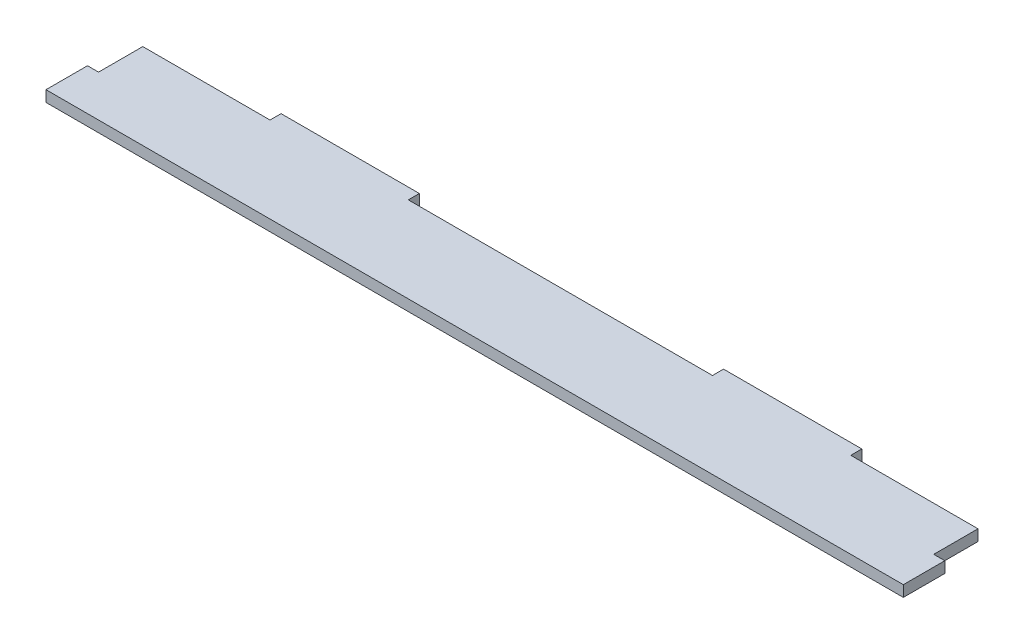
SolidWorks part; units mm, degrees
ref_plane "Alzado" through (0, 0, 0) normal (0, 0, 1) x (1, 0, 0)
ref_plane "Planta" through (0, 0, 0) normal (0, 1, 0) x (1, 0, 0)
ref_plane "Vista lateral" through (0, 0, 0) normal (1, 0, 0) x (0, 0, -1)
sketch "Croquis1" plane through (0, 0, 0) normal (0, 1, 0) x (1, 0, 0)
  line L1 (-155, 17.5) -> (155, 17.5)
  line L2 (-155, 17.5) -> (-155, -17.5)
  line L3 (-155, -17.5) -> (155, -17.5)
  line L4 (155, 17.5) -> (155, -17.5)
  line L5 (-155, 17.5) -> (155, -17.5) construction
  line L6 (-155, -17.5) -> (155, 17.5) construction
  point P0 (0, 0)
  dimension "D1" = 35
  dimension "D2" = 310
extrude "Saliente-Extruir1" add sketch "Croquis1" along normal blind 4
sketch "Croquis2" plane through (0, 4, 0) normal (0, 1, 0) x (1, 0, 0)
  line L0 (-155, 17.5) -> (-155, -17.5) construction
  line L1 (-155, -2.5) -> (-151, -2.5)
  line L2 (-155, -2.5) -> (-155, 17.5)
  line L3 (-155, 17.5) -> (-151, 17.5)
  line L4 (-151, -2.5) -> (-151, 13.5)
  line L5 (-155, -2.5) -> (-151, 17.5) construction
  line L6 (-155, 17.5) -> (-151, -2.5) construction
  line L7 (155, -17.5) -> (155, 17.5) construction
  line L8 (155, -2.5) -> (151, -2.5)
  line L9 (155, -2.5) -> (155, 17.5)
  line L10 (155, 17.5) -> (151, 17.5)
  line L11 (151, -2.5) -> (151, 13.5)
  line L12 (155, -2.5) -> (151, 17.5) construction
  line L13 (155, 17.5) -> (151, -2.5) construction
  line L14 (-155, -17.5) -> (155, -17.5) construction
  line L15 (155, 17.5) -> (-155, 17.5) construction
  line L16 (-151, 13.5) -> (-105, 13.5)
  line L17 (-105, 13.5) -> (-105, 17.5)
  line L18 (-105, 17.5) -> (-151, 17.5)
  line L19 (151, 13.5) -> (105, 13.5)
  line L20 (105, 13.5) -> (105, 17.5)
  line L21 (105, 17.5) -> (151, 17.5)
  line L23 (-55, 17.5) -> (55, 17.5)
  line L24 (-55, 17.5) -> (-55, 13.5)
  line L25 (-55, 13.5) -> (55, 13.5)
  line L26 (55, 17.5) -> (55, 13.5)
  line L27 (-55, 17.5) -> (55, 13.5) construction
  line L28 (-55, 13.5) -> (55, 17.5) construction
  point P4 (-153, 7.5)
  point P11 (153, 7.5)
  point P28 (0, 15.5)
  dimension "D1" = 15
  dimension "D2" = 4
  dimension "D3" = 4
  dimension "D4" = 50
  dimension "D5" = 50
  dimension "D6" = 50
extrude "Cortar-Extruir2" cut sketch "Croquis2" against normal blind 10
equation "\"venesta\"= 4'grosor de la venesta"
equation "\"policarbonato\"= 4'grosor del policarbonato"
equation "\"carton_trupan\"= 3'grosor del carton trupan caso laser"
equation "\"ancho_tot\"= 310'ancho tot sin llantas"
equation "\"largo_tot\"= 400'largo tot sin camera"
equation "\"alto_estimado\"= 300'alto estimado sin lidar"
equation "\"altoparaqpaselabotella\"= 75'alto estimado para que encaje la botella"
equation "\"alturaruedaloca\"= 22"
equation "\"anchoruedaloca\"= 35"
equation "\"anchopiso1motorybaterias\"= 150"
equation "\"dist-pisorampa\"= 5"
equation "\"anchoultimopiso\"= 170"
equation "\"paredtrasera\"= 100"
equation "\"agarradorcanasta\"= 275'recolector"
equation "\"alturapiso1y2\"= 80"
equation "\"alturapiso2y3\"= 80"
equation "\"D1@Croquis1\"=\"anchoruedaloca\""
equation "\"D2@Croquis1\"=\"ancho_tot\""
equation "\"D1@Saliente-Extruir1\"=\"venesta\""
equation "\"D2@Croquis2\"=\"policarbonato\""
equation "\"D3@Croquis2\"=\"policarbonato\""
